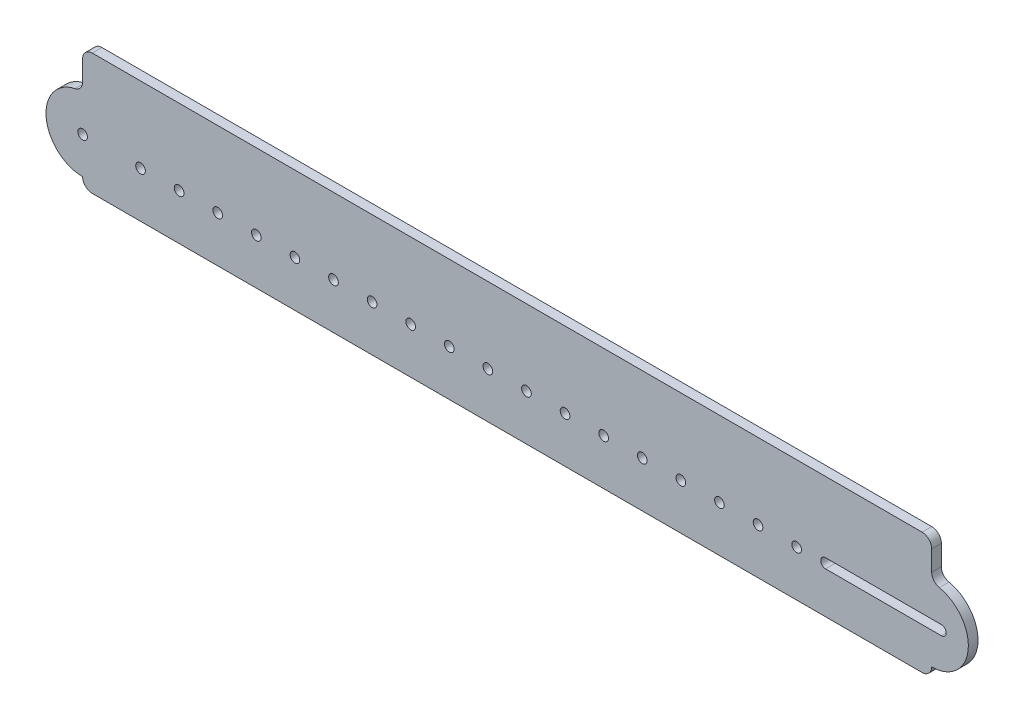
SolidWorks part; units mm, degrees
ref_plane "Front Plane" through (0, 0, 0) normal (0, 0, 1) x (1, 0, 0)
ref_plane "Top Plane" through (0, 0, 0) normal (0, 1, 0) x (1, 0, 0)
ref_plane "Right Plane" through (0, 0, 0) normal (1, 0, 0) x (0, 0, -1)
sketch "Sketch1" plane through (0, 0, 0) normal (0, 0, 1) x (1, 0, 0)
  line L0 (0, 24.13) -> (558.8, 24.13)
  line L1 (0, -24.13) -> (558.8, -24.13)
  line L2 (0, 24.13) -> (558.8, 24.13)
  line L3 (0, 24.13) -> (0, 49.53)
  line L4 (558.8, 24.13) -> (558.8, 49.53)
  line L5 (0, 49.53) -> (558.8, 49.53)
  line L6 (0, -24.13) -> (558.8, -24.13)
  line L7 (0, -24.13) -> (0, -30.48)
  line L8 (558.8, -24.13) -> (558.8, -30.48)
  line L9 (0, -30.48) -> (558.8, -30.48)
  arc A0 (0, 24.13) -> (0, -24.13) centre (0, 0) ccw
  arc A1 (558.8, -24.13) -> (558.8, 24.13) centre (558.8, 0) ccw
  dimension "D1" = 25.4
  dimension "D2" = 24.13
  dimension "D3" = 558.8
  dimension "D4" = 6.35
extrude "Boss-Extrude1" add sketch "Sketch1" along normal mid plane 6.35 contours L5 L3 L0 L4 | L1 A1 L0 A0 | L6 L7 L9 L8 region at (279.4, 36.83, 0) region at (279.4, 0, 0)
sketch "Sketch2" plane through (0, 0, 3.175) normal (0, 0, 1) x (1, 0, 0)
  line L3 (488.95, 3.175) -> (565.15, 3.175)
  line L4 (488.95, -3.175) -> (565.15, -3.175)
  line L5 (558.8, -24.13) -> (558.8, -30.48) construction
  arc A1 (565.15, -3.175) -> (565.15, 3.175) centre (565.15, 0) ccw
  arc A3 (488.95, 3.175) -> (488.95, -3.175) centre (488.95, 0) ccw
  circle A5 centre (0.0009, 0) radius 3.175
  circle A6 centre (0.0009, 0) radius 24.13 construction
  circle A7 centre (38.1, -0.2568) radius 3.175
  circle A8 centre (63.5, -0.2568) radius 3.175
  circle A9 centre (88.9, -0.2568) radius 3.175
  circle A10 centre (114.3, -0.2568) radius 3.175
  circle A11 centre (139.7, -0.2568) radius 3.175
  circle A12 centre (165.1, -0.2568) radius 3.175
  circle A13 centre (190.5, -0.2568) radius 3.175
  circle A14 centre (215.9, -0.2568) radius 3.175
  circle A15 centre (241.3, -0.2568) radius 3.175
  circle A16 centre (266.7, -0.2568) radius 3.175
  circle A17 centre (292.1, -0.2568) radius 3.175
  circle A18 centre (317.5, -0.2568) radius 3.175
  circle A19 centre (342.9, -0.2568) radius 3.175
  circle A20 centre (368.3, -0.2568) radius 3.175
  circle A21 centre (393.7, -0.2568) radius 3.175
  circle A22 centre (419.1, -0.2568) radius 3.175
  circle A23 centre (444.5, -0.2568) radius 3.175
  circle A24 centre (469.9, -0.2568) radius 3.175
  circle A26 centre (495.3, -0.2568) radius 3.175 [skipped]
  arc A27 (558.8, -24.13) -> (558.8, 24.13) centre (558.8, 0) ccw construction
  point P10 (0, 0)
  point P46 (0, 0)
  point P47 (0, 0)
  point P53 (582.93, 0)
  point P54 (0, 0)
  dimension "D1" = 38.1
  dimension "D5" = 69.85
  dimension "D3" = 76.2
  dimension "D4" = 25.4
  dimension "D2" = 19
extrude "Cut-Extrude1" cut sketch "Sketch2" against normal through all
fillet "Fillet1" radius 6.35 6 edges at (0, 24.13, 0) (558.8, 24.13, 0) (558.8, 49.53, 0) (0, 49.53, 0) (0, -30.48, 0) (558.8, -30.48, 0)
sketch "Sketch3" plane through (0, -30.48, 0) normal (0, 1, 0) x (1, 0, 0)
  line L4 (25.4, 3.175) -> (533.4, 3.175)
  line L5 (25.4, 3.175) -> (25.4, 15.875)
  line L6 (533.4, 3.175) -> (533.4, 15.875)
  line L7 (25.4, 15.875) -> (533.4, 15.875)
  line L8 (6.35, 3.175) -> (552.45, 3.175) construction
  line L9 (6.35, -3.175) -> (552.45, -3.175) construction
  point P10 (279.4, -3.175)
  point P11 (279.4, 15.875)
  dimension "D1" = 508
  dimension "D2" = 12.7
extrude "Boss-Extrude2" [suppressed] add sketch "Sketch3" along normal blind 2.54
sketch "Sketch4" [suppressed] plane through (0, 0, -15.875) normal (0, 0, -1) x (-1, 0, 0)
  line L0 (-38.1, -30.7975) -> (-38.1, -33.3375)
  line L5 (-546.1, -30.7975) -> (-546.1, -33.3375)
  line L6 (-546.1, -33.3375) -> (-617.5744, -59.3521)
  line L7 (-546.1, -30.7975) -> (-618.3908, -57.1092)
  line L8 (-38.1, -30.7975) -> (-546.1, -30.7975) construction
  arc A4 (-618.3908, -57.1092) -> (-617.5744, -59.3521) centre (-617.9826, -58.2306) ccw
  dimension "D3" = 46.0152
  dimension "D4" = 200
extrude "Boss-Extrude3" [suppressed] add sketch "Sketch4" against normal blind 2.54 contours L6 A4 L7 L5
